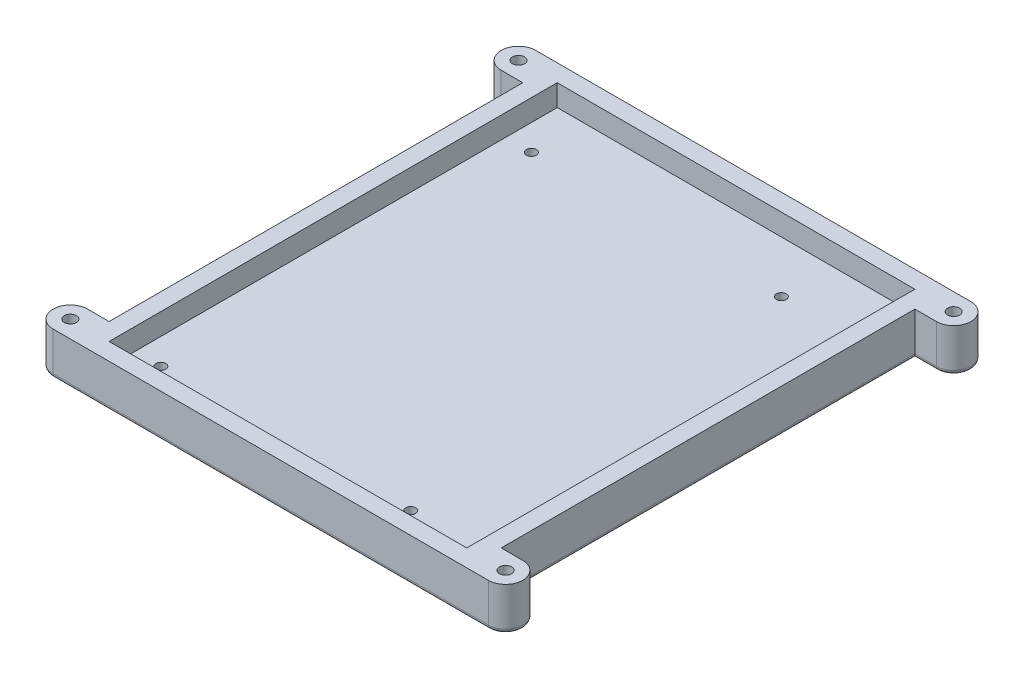
SolidWorks part; units mm, degrees
ref_plane "Front Plane" through (0, 0, 0) normal (0, 0, 1) x (1, 0, 0)
ref_plane "Top Plane" through (0, 0, 0) normal (0, 1, 0) x (1, 0, 0)
ref_plane "Right Plane" through (0, 0, 0) normal (1, 0, 0) x (0, 0, -1)
sketch "Sketch1" plane through (0, 0, 0) normal (0, 1, 0) x (1, 0, 0)
  line L0 (0, 56) -> (0, -56) construction
  line L1 (-39.5, 50) -> (39.5, 50) construction
  line L2 (-39.5, 50) -> (-39.5, -50) construction
  line L3 (-39.5, -50) -> (39.5, -50) construction
  line L4 (39.5, 50) -> (39.5, -50) construction
  line L5 (-45.5, 56) -> (45.5, 56)
  line L6 (-45.5, 56) -> (-45.5, -56)
  line L7 (-45.5, -56) -> (45.5, -56)
  line L8 (45.5, 56) -> (45.5, -56)
  circle A0 centre (-35.5, -46) radius 1.15
  circle A1 centre (22.5, -46) radius 1.15
  circle A2 centre (22.5, 40) radius 1.15
  circle A3 centre (-35.5, 40) radius 1.15
  point P4 (-39.5, 0)
  point P6 (0, 50)
  dimension "D5" = 2.3
  dimension "D6" = 86
  dimension "D7" = 58
  dimension "D8" = 4
  dimension "D9" = 4
  dimension "D1" = 79
  dimension "D2" = 100
  dimension "D3" = 112
  dimension "D4" = 91
extrude "Base" add sketch "Sketch1" along normal blind 10
sketch "Sketch2" plane through (0, 10, 0) normal (0, 1, 0) x (1, 0, 0)
  line L0 (0, 52) -> (0, -52) construction
  line L1 (-41.5, 52) -> (41.5, 52)
  line L2 (-41.5, 52) -> (-41.5, -52)
  line L3 (-41.5, -52) -> (41.5, -52)
  line L4 (41.5, 52) -> (41.5, -52)
  line L5 (-45.5, -56) -> (45.5, -56) construction
  line L6 (-45.5, 56) -> (-45.5, -56) construction
  dimension "D1" = 4
  dimension "D2" = 4
extrude "Module Cutout" cut sketch "Sketch2" against normal blind 5
sketch "Sketch3" plane through (0, 10, 0) normal (0, 1, 0) x (1, 0, 0)
  line L0 (-45.5, 56) -> (-50.5, 56)
  line L1 (-45.5, 56) -> (-45.5, -56) construction
  line L2 (-45.5, 56) -> (-45.5, 48)
  line L3 (-45.5, 48) -> (-50.5, 48)
  line L4 (45.5, 56) -> (-45.5, 56) construction
  line L5 (0, 56) -> (0, -56) construction
  line L6 (-45.5, -56) -> (45.5, -56) construction
  line L7 (45.5, 48) -> (50.5, 48)
  line L8 (45.5, 56) -> (45.5, 48)
  line L9 (45.5, 56) -> (50.5, 56)
  line L10 (-45.5, 0) -> (45.5, 0) construction
  line L11 (45.5, -56) -> (45.5, 56) construction
  line L12 (45.5, -56) -> (50.5, -56)
  line L13 (45.5, -56) -> (45.5, -48)
  line L14 (45.5, -48) -> (50.5, -48)
  line L15 (-45.5, -48) -> (-50.5, -48)
  line L16 (-45.5, -56) -> (-45.5, -48)
  line L17 (-45.5, -56) -> (-50.5, -56)
  arc A0 (-50.5, 48) -> (-50.5, 56) centre (-50.5, 52) cw
  circle A1 centre (-50.5, 52) radius 1.4
  circle A2 centre (50.5, 52) radius 1.4
  arc A3 (50.5, 48) -> (50.5, 56) centre (50.5, 52) ccw
  arc A4 (50.5, -48) -> (50.5, -56) centre (50.5, -52) cw
  circle A5 centre (50.5, -52) radius 1.4
  circle A6 centre (-50.5, -52) radius 1.4
  arc A7 (-50.5, -48) -> (-50.5, -56) centre (-50.5, -52) ccw
  dimension "D1" = 2.8
  dimension "D2" = 8
  dimension "D3" = 5
extrude "Case Assembly Holes" add sketch "Sketch3" against normal up to surface (10 mm away) up to face at (0, 0, 0)
sketch "Sketch4" plane through (0, 0, 0) normal (0, -1, 0) x (1, 0, 0)
  line L0 (0, 25) -> (0, -25) construction
  line L1 (-15, 25) -> (15, 25) construction
  line L2 (-15, 25) -> (-15, -25) construction
  line L3 (-15, -25) -> (15, -25) construction
  line L4 (15, 25) -> (15, -25) construction
  circle A0 centre (-15, 25) radius 1.4
  circle A1 centre (-15, -25) radius 1.4
  circle A2 centre (15, -25) radius 1.4
  circle A3 centre (15, 25) radius 1.4
  point P7 (-15, 0)
  dimension "D3" = 2.8
  dimension "D1" = 30
  dimension "D2" = 50
extrude "Basket Clamp Mounting Holes" cut sketch "Sketch4" against normal blind 4
fillet "1mm Edge Fillets" radius 1 12 edges at (48, 0, 48) (-48, 0, 48) (-54.5, 0, 52) (0, 0, 56) (48, 0, -48) (54.5, 0, -52) (-48, 0, -48) (-54.5, 0, -52) (-45.5, 0, 0) (54.5, 0, 52) (45.5, 0, 0) (0, 0, -56)
